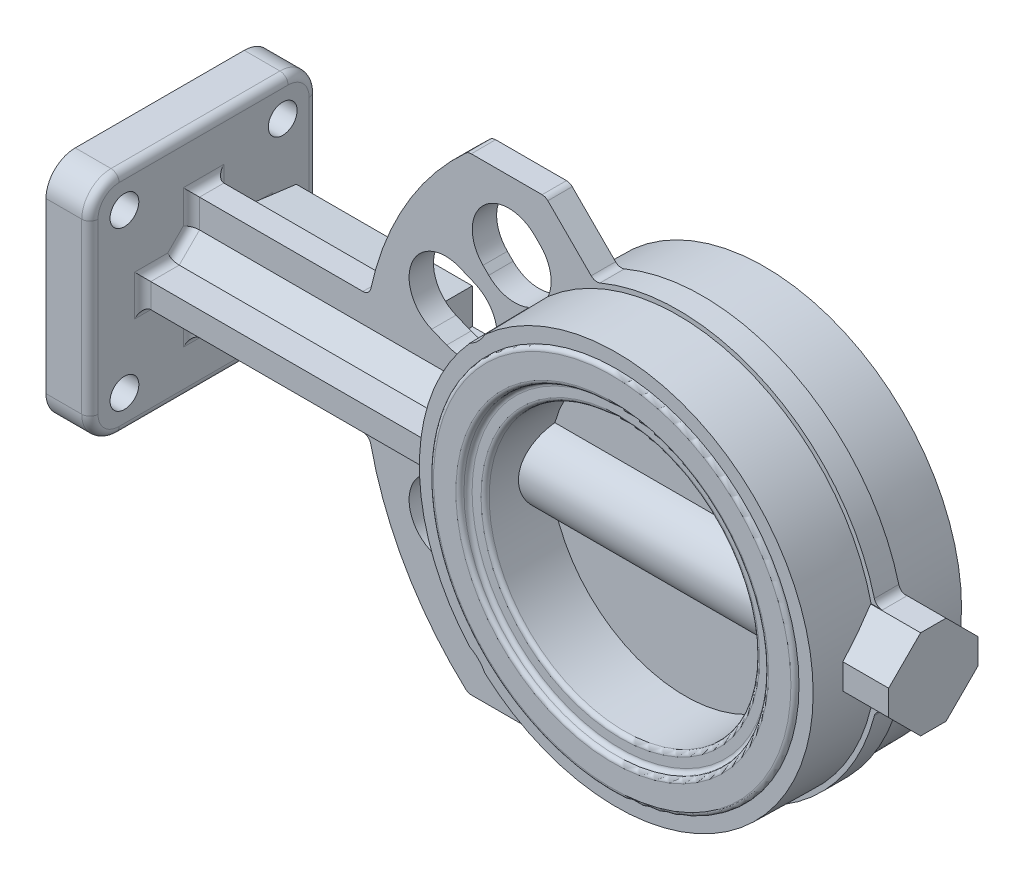
SolidWorks part; units mm, degrees
material "A36"
ref_plane "Front Plane" through (0, 0, 0) normal (0, 0, 1) x (1, 0, 0)
ref_plane "Top Plane" through (0, 0, 0) normal (0, 1, 0) x (1, 0, 0)
ref_plane "Right Plane" through (0, 0, 0) normal (1, 0, 0) x (0, 0, -1)
sketch "Sketch1" plane through (0, 0, 0) normal (0, 0, 1) x (1, 0, 0)
  circle A0 centre (0, 0) radius 61.976
  dimension "D1" = 123.952
extrude "Boss-Extrude1" add sketch "Sketch1" along normal mid plane 46.3931 draft 1
sketch "Sketch2" plane through (0, 0, 23.1965) normal (0, 0, 1) x (1, 0, 0)
  circle A0 centre (0, 0) radius 57.15
  dimension "D1" = 114.3
extrude "Boss-Extrude2" add sketch "Sketch2" along normal blind 1.27
sketch "Sketch3" plane through (0, 0, -23.1965) normal (0, 0, -1) x (-1, 0, 0)
  circle A0 centre (0, 0) radius 57.15
  dimension "D1" = 114.3
extrude "Boss-Extrude3" add sketch "Sketch3" along normal blind 1.27
sketch "Sketch4" plane through (0, 0, -24.4666) normal (0, 0, -1) x (-1, 0, 0)
  circle A0 centre (0, 0) radius 47.625
  dimension "D1" = 95.25
extrude "Cut-Extrude1" cut sketch "Sketch4" against normal blind 2.54
sketch "Sketch5" plane through (0, 0, 24.4666) normal (0, 0, 1) x (1, 0, 0)
  circle A0 centre (0, 0) radius 47.625
  dimension "D1" = 95.25
extrude "Cut-Extrude2" cut sketch "Sketch5" against normal blind 2.54
sketch "Sketch6" plane through (0, 0, 21.9265) normal (0, 0, 1) x (1, 0, 0)
  circle A0 centre (0, 0) radius 42.291
  dimension "D1" = 84.582
extrude "Cut-Extrude3" cut sketch "Sketch6" against normal through all
sketch "Sketch7" plane through (0, 0, 0) normal (0, 1, 0) x (1, 0, 0)
  line L1 (-63.3491, 3.81) -> (-56.9991, 3.81)
  line L2 (-63.3491, 3.81) -> (-63.3491, -3.81)
  line L3 (-63.3491, -3.81) -> (-56.9991, -3.81)
  line L4 (-56.9991, 3.81) -> (-56.9991, -3.81)
  line L5 (-63.3491, 0) -> (-61.976, 0) construction
  line L7 (0, 0) -> (0, 23.1965) construction
  line L8 (61.5711, 23.1965) -> (-61.5711, 23.1965) construction
  dimension "D1" = 7.62
  dimension "D2" = 1.778
  dimension "D3" = 6.35
revolve "Revolve1" add sketch "Sketch7" angle 360 about L7
ref_plane "Plane1" through (57.15, 0, 0) normal (1, 0, 0) x (0, 0, -1)
sketch "Sketch8" plane through (57.15, 0, 0) normal (1, 0, 0) x (0, 0, -1)
  line L1 (-13.97, 13.97) -> (13.97, 13.97)
  line L2 (-13.97, 13.97) -> (-13.97, -13.97)
  line L3 (-13.97, -13.97) -> (13.97, -13.97)
  line L4 (13.97, 13.97) -> (13.97, -13.97)
  line L5 (-13.97, 13.97) -> (13.97, -13.97) construction
  line L6 (-13.97, -13.97) -> (13.97, 13.97) construction
  point P0 (0, 0)
  dimension "D1" = 27.94
extrude "Boss-Extrude4" add sketch "Sketch8" along normal blind 18.796
chamfer "Chamfer1" distance 10 angle 45 4 edges at (68.0383, 13.97, -13.97) (68.0383, -13.97, -13.97) (68.0383, -13.97, 13.97) (68.0383, 13.97, 13.97)
ref_plane "Plane2" through (-63.3491, 0, 0) normal (-1, 0, 0) x (0, 0, 1)
sketch "Sketch9" plane through (-63.3491, 0, 0) normal (-1, 0, 0) x (0, 0, 1)
  line L0 (-3.81, 63.3491) -> (-3.81, -63.3491) construction
  line L1 (-19.05, 3.81) -> (-3.81, 3.81)
  line L2 (-19.05, 3.81) -> (-19.05, -3.81)
  line L3 (-19.05, -3.81) -> (-3.81, -3.81)
  line L4 (19.05, 3.81) -> (19.05, -3.81)
  line L5 (-19.05, 3.81) -> (19.05, -3.81) construction
  line L6 (-19.05, -3.81) -> (19.05, 3.81) construction
  line L7 (-3.81, -19.05) -> (3.81, -19.05)
  line L8 (-3.81, -19.05) -> (-3.81, -3.81)
  line L9 (-3.81, 19.05) -> (3.81, 19.05)
  line L10 (3.81, -19.05) -> (3.81, -3.81)
  line L11 (-3.81, -19.05) -> (3.81, 19.05) construction
  line L12 (-3.81, 19.05) -> (3.81, -19.05) construction
  line L13 (3.81, 3.81) -> (19.05, 3.81)
  line L14 (-3.81, 3.81) -> (-3.81, 19.05)
  line L15 (3.81, 3.81) -> (3.81, 19.05)
  line L19 (3.81, -3.81) -> (19.05, -3.81)
  point P0 (0, 0)
  point P5 (0, 0)
  dimension "D1" = 38.1
  dimension "D2" = 38.1
extrude "Boss-Extrude5" add sketch "Sketch9" along normal blind 88.9 and the other way blind 12.7
sketch "Sketch10" plane through (0, 0, -3.81) normal (0, 0, -1) x (-1, 0, 0)
  line L0 (60.4169, -19.05) -> (152.2491, -19.05) construction
  line L1 (26.0122, 57.7622) -> (41.5287, 73.2787)
  line L2 (0, 0) -> (-31.75, 0) construction
  line L3 (26.0122, -57.7622) -> (41.5287, -73.2787)
  line L4 (26.0122, 57.7622) -> (-31.75, 0) construction
  line L5 (41.5287, 73.2787) -> (65.7093, 73.2787)
  line L6 (41.5287, -73.2787) -> (65.7093, -73.2787)
  line L7 (60.4169, 19.05) -> (152.2491, 19.05) construction
  line L8 (60.4169, -19.05) -> (96.5639, -19.05)
  line L9 (60.4169, 19.05) -> (96.5639, 19.05)
  line L10 (-31.75, 0) -> (26.0122, -57.7622) construction
  arc A0 (65.7093, -73.2787) -> (96.5639, -19.05) centre (0, 0) ccw
  arc A1 (-61.7895, -13.97) -> (60.4169, -19.05) centre (0, 0) ccw construction
  arc A2 (60.4169, 19.05) -> (-61.7895, 13.97) centre (0, 0) ccw construction
  arc A3 (26.0122, -57.7622) -> (60.4169, -19.05) centre (0, 0) ccw
  arc A4 (60.4169, 19.05) -> (26.0122, 57.7622) centre (0, 0) ccw
  arc A5 (96.5639, 19.05) -> (65.7093, 73.2787) centre (0, 0) ccw
  dimension "D1" = 196.85
  dimension "D2" = 146.5574
  dimension "D3" = 90
  dimension "D5" = 31.75
extrude "Boss-Extrude6" add sketch "Sketch10" against normal up to surface (7.62 mm away) up to face at (-51.1757, 28.8751, 3.81)
sketch "Sketch11" plane through (-152.2491, 0, 0) normal (-1, 0, 0) x (0, 0, 1)
  line L1 (35.56, 35.56) -> (-35.56, 35.56)
  line L2 (35.56, 35.56) -> (35.56, -35.56)
  line L3 (35.56, -35.56) -> (-35.56, -35.56)
  line L4 (-35.56, 35.56) -> (-35.56, -35.56)
  line L5 (35.56, 35.56) -> (-35.56, -35.56) construction
  line L6 (35.56, -35.56) -> (-35.56, 35.56) construction
  point P0 (0, 0)
  dimension "D1" = 71.12
extrude "Boss-Extrude7" add sketch "Sketch11" along normal blind 13.716
chamfer "Chamfer2" distance 6.35 angle 45 2 edges at (-107.0206, 3.81, 3.81) (-107.0206, -3.81, 3.81)
fillet "Fillet1" radius 9.144 4 edges at (-159.1071, 35.56, -35.56) (-159.1071, 35.56, 35.56) (-159.1071, -35.56, -35.56) (-159.1071, -35.56, 35.56)
sketch "Sketch12" plane through (0, 0, -3.81) normal (0, 0, -1) x (-1, 0, 0)
  line L0 (152.2491, 26.416) -> (152.2491, -26.416) construction
  line L1 (143.3591, 15.875) -> (86.2091, 15.875)
  line L2 (143.3591, 15.875) -> (143.3591, -15.875)
  line L3 (143.3591, -15.875) -> (86.2091, -15.875)
  line L4 (86.2091, 15.875) -> (86.2091, -15.875)
  line L5 (143.3591, 15.875) -> (86.2091, -15.875) construction
  line L6 (143.3591, -15.875) -> (86.2091, 15.875) construction
  line L7 (114.7841, 0) -> (0, 0) construction
  point P0 (114.7841, 0)
  dimension "D1" = 57.15
  dimension "D2" = 31.75
  dimension "D3" = 8.89
extrude "Boss-Extrude8" add sketch "Sketch12" along normal up to surface (15.24 mm away) draft 4
sketch "Sketch13" plane through (0, 0, -3.81) normal (0, 0, -1) x (-1, 0, 0)
  line L0 (72.7463, 30.1325) -> (68.053, 28.1885) construction
  line L1 (77.1203, 19.5726) -> (72.427, 17.6285)
  line L2 (68.3722, 40.6924) -> (63.6789, 38.7484)
  line L3 (52.9835, 52.9835) -> (51.1875, 51.1875) construction
  line L4 (61.0657, 44.9013) -> (59.2697, 43.1052)
  line L5 (44.9013, 61.0657) -> (43.1052, 59.2697)
  line L6 (72.7463, -30.1325) -> (68.053, -28.1885) construction
  line L7 (68.3722, -40.6924) -> (63.6789, -38.7484)
  line L8 (77.1203, -19.5726) -> (72.427, -17.6285)
  line L9 (52.9835, -52.9835) -> (51.1875, -51.1875) construction
  line L10 (44.9013, -61.0657) -> (43.1052, -59.2697)
  line L11 (61.0657, -44.9013) -> (59.2697, -43.1052)
  line L12 (0, 0) -> (52.0855, 52.0855) construction
  line L13 (0, 0) -> (70.3996, 29.1605) construction
  line L14 (0, 0) -> (70.3996, -29.1605) construction
  line L15 (0, 0) -> (52.0855, -52.0855) construction
  line L16 (0, 0) -> (165.9651, 0) construction
  line L17 (165.9651, 26.416) -> (165.9651, -26.416) construction
  arc A0 (77.1203, 19.5726) -> (68.3722, 40.6924) centre (72.7463, 30.1325) ccw
  arc A1 (63.6789, 38.7484) -> (72.427, 17.6285) centre (68.053, 28.1885) ccw
  arc A2 (61.0657, 44.9013) -> (44.9013, 61.0657) centre (52.9835, 52.9835) ccw
  arc A3 (43.1052, 59.2697) -> (59.2697, 43.1052) centre (51.1875, 51.1875) ccw
  arc A4 (68.3722, -40.6924) -> (77.1203, -19.5726) centre (72.7463, -30.1325) ccw
  arc A5 (72.427, -17.6285) -> (63.6789, -38.7484) centre (68.053, -28.1885) ccw
  arc A6 (44.9013, -61.0657) -> (61.0657, -44.9013) centre (52.9835, -52.9835) ccw
  arc A7 (59.2697, -43.1052) -> (43.1052, -59.2697) centre (51.1875, -51.1875) ccw
  point P2 (70.3996, 29.1605)
  point P7 (52.0855, 52.0855)
  point P14 (70.3996, -29.1605)
  point P21 (52.0855, -52.0855)
  dimension "D1" = 11.43
  dimension "D2" = 11.43
  dimension "D3" = 2.54
  dimension "D4" = 5.08
  dimension "D5" = 22.5
  dimension "D6" = 45
  dimension "D7" = 22.5
  dimension "D8" = 45
  dimension "D9" = 73.66
  dimension "D10" = 73.66
  dimension "D11" = 76.2
  dimension "D12" = 76.2
extrude "Cut-Extrude4" cut sketch "Sketch13" against normal through all and the other way through all
fillet "Fillet2" radius 1.27 7 edges at (47.625, 0, 21.9265) (42.291, 0, 21.9265) (-42.291, 0, -21.9265) (57.15, 0, 24.4666) (47.625, 0, 24.4666) (-57.15, 0, -24.4666) (-47.625, 0, -24.4666)
fillet "Fillet3" radius 2.54 33 edges at (-152.2491, 0, 19.05) (-152.2491, -3.81, 14.605) (-152.2491, -6.985, 6.985) (-152.2491, -14.605, 3.81) (-152.2491, -19.05, 0) (-152.2491, -14.605, -3.81) (-152.2491, -6.985, -6.985) (-152.2491, -3.81, -14.605) (-152.2491, 0, -19.05) (-152.2491, 3.81, -14.605) (-152.2491, 6.985, -6.985) (-152.2491, 19.05, 0) (-152.2491, 14.605, 3.81) (-152.2491, 6.985, 6.985) (-152.2491, 3.81, 14.605) (61.7895, 13.97, 0) (61.7895, -13.97, 0) (-96.5639, -19.05, 0) (-96.5639, 19.05, 0) (-26.0122, -57.7622, 0) (-26.0122, 57.7622, 0) (-41.5287, 73.2787, 0) (-65.7093, 73.2787, 0) (-41.5287, -73.2787, 0) (-65.7093, -73.2787, 0) (-152.2491, -32.8818, -32.8818) (-152.2491, -35.56, 0) (-152.2491, -32.8818, 32.8818) (-152.2491, 0, 35.56) (-152.2491, 32.8818, 32.8818) (-152.2491, 35.56, 0) (-152.2491, 32.8818, -32.8818) (-152.2491, 0, -35.56)
sketch "Sketch14" plane through (-165.9651, 0, 0) normal (-1, 0, 0) x (0, 0, 1)
  circle A0 centre (0, 0) radius 9.525
  dimension "D1" = 19.05
extrude "Cut-Extrude5" cut sketch "Sketch14" against normal blind 7.62
hole_wizard "M8 Clearance Hole1" positions "Sketch16" profile "Sketch17" hole size "M8" standard "ANSI Metric"
sketch "Sketch16" plane through (-165.9651, 0, 0) normal (-1, 0, 0) x (0, 0, 1)
  line L1 (-24.7487, 24.7487) -> (24.7487, 24.7487)
  line L2 (-24.7487, 24.7487) -> (-24.7487, -24.7487)
  line L3 (-24.7487, -24.7487) -> (24.7487, -24.7487)
  line L4 (24.7487, 24.7487) -> (24.7487, -24.7487)
  line L5 (0, 0) -> (0, 24.7487)
  line L6 (0, 0) -> (0, -24.7487)
  point P0 (-24.7487, 24.7487)
  point P2 (24.7487, 24.7487)
  point P4 (24.7487, -24.7487)
  point P6 (-24.7487, -24.7487)
  dimension "D1" = 70
sketch "Sketch17" plane through (-165.9651, 24.7487, -24.7487) normal (0, 1, 0) x (0, 0, 1)
  line L0 (0, 0) -> (0, 13.716)
  line L1 (0, 13.716) -> (4.5, 13.716)
  line L2 (4.5, 13.716) -> (4.5, 0)
  line L5 (4.5, 0) -> (0, 0)
  line L11 (0, -6.35) -> (0, 107.95) construction
  dimension "Thru Hole Dia." = 9
  dimension "Thru Hole Depth" = 13.716
sketch "Sketch18" plane through (75.946, 0, 0) normal (1, 0, 0) x (0, 0, -1)
  circle A0 centre (0, 0) radius 11.5
  dimension "D1" = 23
extrude "Boss-Extrude9" add sketch "Sketch18" against normal blind 127
sketch "Sketch19" plane through (-158.3451, 0, 0) normal (-1, 0, 0) x (0, 0, 1)
  circle A0 centre (0, 0) radius 7
  dimension "D1" = 14
extrude "Boss-Extrude10" add sketch "Sketch19" along normal offset from surface (6.62 mm away) 1 up to face at (-165.9651, -24.7487, -20.2487)
sketch "Sketch20" plane through (-164.9651, 0, 0) normal (-1, 0, 0) x (0, 0, 1)
  line L0 (0, 7.7782) -> (-7.7782, 0)
  line L5 (0, -7.7782) -> (7.7782, 0)
  line L6 (7.7782, 0) -> (0, 7.7782)
  line L7 (-7.7782, 0) -> (0, -7.7782)
  line L8 (-7.7782, 0) -> (7.7782, 0) construction
  line L9 (0, 7.7782) -> (0, -7.7782) construction
  point P4 (0, 0)
  dimension "D1" = 11
  dimension "D2" = 90
extrude "Boss-Extrude11" add sketch "Sketch20" along normal blind 19
chamfer "Chamfer3" distance 1.5 angle 45 4 edges at (-174.4651, -7.7782, 0) (-174.4651, 0, 7.7782) (-174.4651, 7.7782, 0) (-174.4651, 0, -7.7782)
sketch "Sketch21" plane through (0, 0, 0) normal (0, 0, 1) x (1, 0, 0)
  circle A0 centre (0, 0) radius 42.291
extrude "Boss-Extrude12" add sketch "Sketch21" along normal mid plane 3.33
